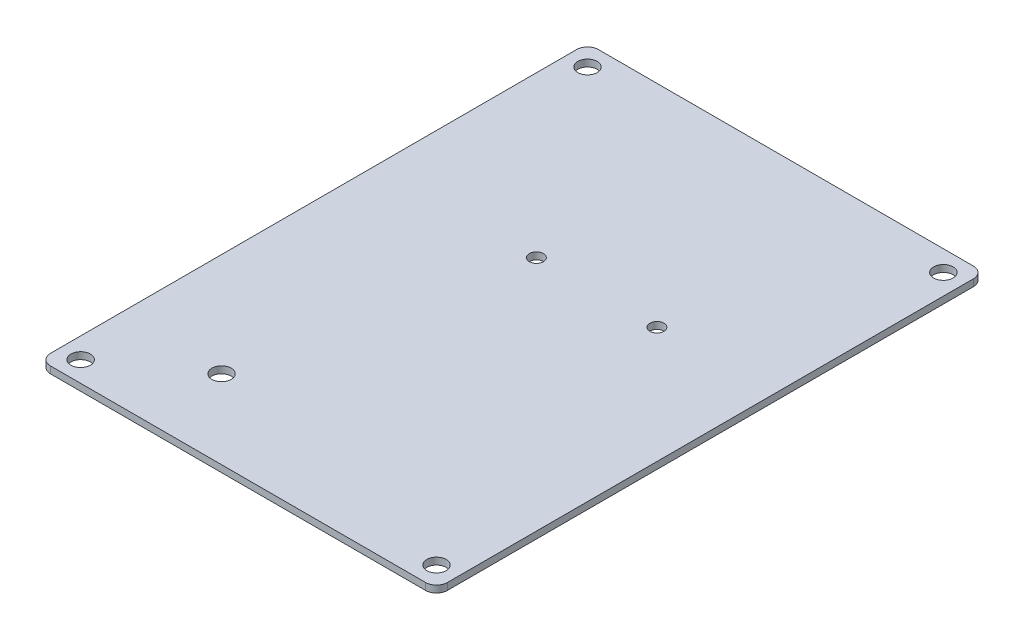
SolidWorks part; units mm, degrees
ref_plane "Front" through (0, 0, 0) normal (0, 0, 1) x (1, 0, 0)
ref_plane "Top" through (0, 0, 0) normal (0, 1, 0) x (1, 0, 0)
ref_plane "Right" through (0, 0, 0) normal (1, 0, 0) x (0, 0, -1)
sketch "Sketch1" plane through (0, 0, 0) normal (0, 1, 0) x (1, 0, 0)
  line L1 (-46, -63.5) -> (46, -63.5)
  line L2 (-46, -63.5) -> (-46, 63.5)
  line L3 (-46, 63.5) -> (46, 63.5)
  line L4 (46, -63.5) -> (46, 63.5)
  line L5 (-46, -63.5) -> (46, 63.5) construction
  line L6 (-46, 63.5) -> (46, -63.5) construction
  point P0 (0, 0)
  dimension "D1" = 127
  dimension "D2" = 92
extrude "Boss-Extrude1" add sketch "Sketch1" along normal blind 1.6
hole_wizard "M4 Clearance Hole1" positions "Sketch2" profile "Sketch3" hole size "M4" standard "ANSI Metric"
sketch "Sketch2" plane through (0, 1.6, 0) normal (0, 1, 0) x (1, 0, 0)
  line L1 (-41.2375, 58.7375) -> (41.2375, 58.7375)
  line L2 (-41.2375, 58.7375) -> (-41.2375, -58.7375)
  line L3 (-41.2375, -58.7375) -> (41.2375, -58.7375)
  line L4 (41.2375, 58.7375) -> (41.2375, -58.7375)
  line L5 (-41.2375, 58.7375) -> (41.2375, -58.7375) construction
  line L6 (-41.2375, -58.7375) -> (41.2375, 58.7375) construction
  line L7 (46, -63.5) -> (46, 63.5) construction
  line L8 (-46, -63.5) -> (46, -63.5) construction
  point P0 (-41.2375, 58.7375)
  point P2 (41.2375, 58.7375)
  point P4 (41.2375, -58.7375)
  point P6 (-41.2375, -58.7375)
  dimension "D1" = 4.7625
  dimension "D2" = 4.7625
sketch "Sketch3" plane through (-41.2375, 1.6, -58.7375) normal (1, 0, 0) x (0, 0, 1)
  line L0 (0, 0) -> (0, 51.3519)
  line L1 (0, 51.3519) -> (2.25, 50)
  line L2 (2.25, 50) -> (2.25, 0)
  line L5 (2.25, 0) -> (0, 0)
  line L10 (0, 51.3519) -> (-2.25, 50) construction
  line L11 (0, -6.35) -> (0, 107.95) construction
  dimension "Hole Dia." = 4.5
  dimension "Hole Depth" = 50
  dimension "Drill Angle" = 118
fillet "Fillet1" radius 2.54 4 edges at (46, 0.8, 63.5) (46, 0.8, -63.5) (-46, 0.8, -63.5) (-46, 0.8, 63.5)
hole_wizard "#4 Clearance Hole1" positions "Sketch4" profile "Sketch5" hole size "#4" standard "ANSI Inch"
sketch "Sketch4" plane through (0, 1.6, 0) normal (0, 1, 0) x (1, 0, 0)
  line L1 (46, -60.96) -> (46, 60.96) construction
  line L2 (43.46, 63.5) -> (-43.46, 63.5) construction
  line L3 (-46, 60.96) -> (-46, -60.96) construction
  point P22 (19.05, 14.54)
  point P24 (-8.89, 14.54)
  point P27 (0, 0)
  point P28 (0, 0)
  point P29 (0, 0)
  point P30 (0, 0)
  dimension "D1" = 26.95
  dimension "D2" = 48.96
  dimension "D3" = 48.96
  dimension "D4" = 37.11
sketch "Sketch5" plane through (19.05, 1.6, -14.54) normal (1, 0, 0) x (0, 0, 1)
  line L0 (0, 0) -> (0, 19.7306)
  line L1 (0, 19.7306) -> (1.6319, 18.75)
  line L2 (1.6319, 18.75) -> (1.6319, 0)
  line L5 (1.6319, 0) -> (0, 0)
  line L10 (0, 19.7306) -> (-1.632, 18.75) construction
  line L11 (0, -6.35) -> (0, 107.95) construction
  dimension "Hole Dia." = 3.2639
  dimension "Hole Depth" = 18.75
  dimension "Drill Angle" = 118
hole_wizard "#8 Clearance Hole1" positions "Sketch6" profile "Sketch7" hole size "#8" standard "ANSI Inch"
sketch "Sketch6" plane through (0, 0, 0) normal (0, -1, 0) x (-1, 0, 0)
  circle A0 centre (22.07, -45.25) radius 1.5 construction
  point P0 (22.07, -45.25)
  point P3 (0, 0)
sketch "Sketch7" plane through (-22.07, 0, 45.25) normal (1, 0, 0) x (0, 0, -1)
  line L0 (0, 0) -> (0, 20.1007)
  line L1 (0, 20.1007) -> (2.2479, 18.75)
  line L2 (2.2479, 18.75) -> (2.2479, 0)
  line L5 (2.2479, 0) -> (0, 0)
  line L10 (0, 20.1007) -> (-2.2479, 18.75) construction
  line L11 (0, -6.35) -> (0, 107.95) construction
  dimension "Hole Dia." = 4.4958
  dimension "Hole Depth" = 18.75
  dimension "Drill Angle" = 118
